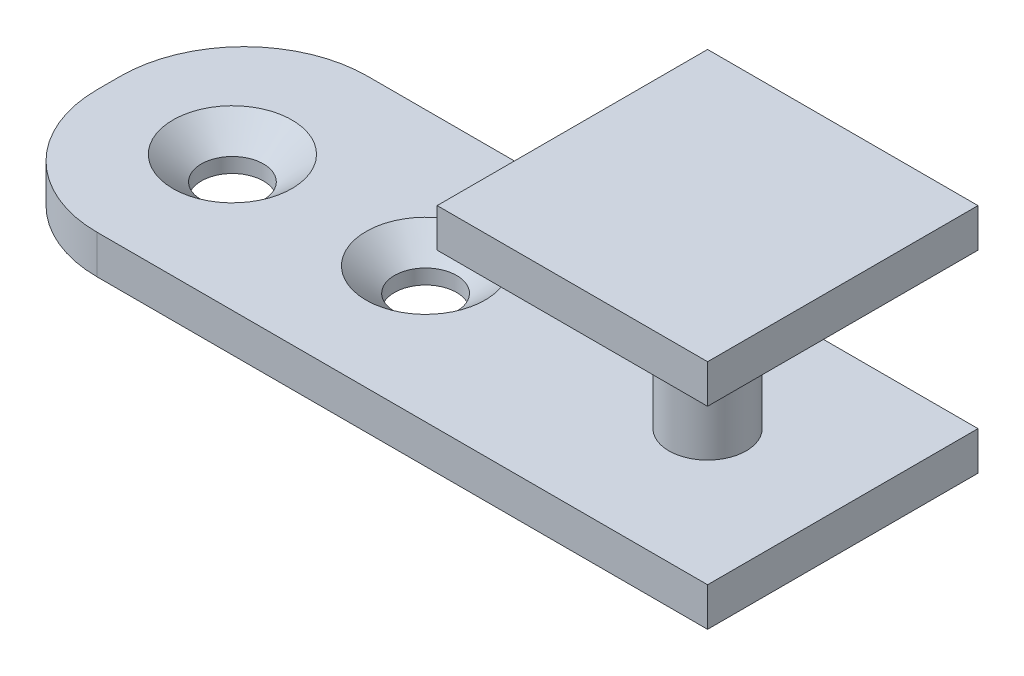
SolidWorks part; units mm, degrees
ref_plane "Front Plane" through (0, 0, 0) normal (0, 0, 1) x (1, 0, 0)
ref_plane "Top Plane" through (0, 0, 0) normal (0, 1, 0) x (1, 0, 0)
ref_plane "Right Plane" through (0, 0, 0) normal (1, 0, 0) x (0, 0, -1)
sketch "Sketch1" plane through (0, 0, 0) normal (0, 1, 0) x (1, 0, 0)
  circle A0 centre (0, 0) radius 3.175
  dimension "D1" = 6.35
extrude "Boss-Extrude1" add sketch "Sketch1" along normal blind 12.7
sketch "Sketch2" plane through (0, 12.7, 0) normal (0, 1, 0) x (1, 0, 0)
  line L1 (-11.1125, -11.1125) -> (11.1125, -11.1125)
  line L2 (-11.1125, -11.1125) -> (-11.1125, 11.1125)
  line L3 (-11.1125, 11.1125) -> (11.1125, 11.1125)
  line L4 (11.1125, -11.1125) -> (11.1125, 11.1125)
  line L5 (-11.1125, -11.1125) -> (11.1125, 11.1125) construction
  line L6 (-11.1125, 11.1125) -> (11.1125, -11.1125) construction
  point P0 (0, 0)
  dimension "D1" = 22.225
  dimension "D2" = 22.225
extrude "Boss-Extrude2" add sketch "Sketch2" along normal blind 3.175 contours L2 L3 L4 L1
ref_plane "Plane1" through (0, 6.35, 0) normal (0, -1, 0) x (-1, 0, 0)
mirror "Mirror1" about plane through (0, 6.35, 0) normal (0, -1, 0) of "Boss-Extrude2"
ref_axis "Axis1" through (0, 12.7, 0) along (0, -1, 0)
sketch "Sketch3" plane through (0, -3.175, 0) normal (0, -1, 0) x (1, 0, 0)
  line L0 (-11.1125, 11.1125) -> (11.1125, 11.1125) construction
  line L1 (-11.1125, -11.1125) -> (-39.0525, -11.1125)
  line L2 (-11.1125, -11.1125) -> (-11.1125, 11.1125)
  line L3 (-11.1125, 11.1125) -> (-39.0525, 11.1125)
  line L4 (-49.2125, -0.9525) -> (-49.2125, 0.9525)
  arc A0 (-49.2125, -0.9525) -> (-39.0525, -11.1125) centre (-39.0525, -0.9525) ccw
  arc A1 (-49.2125, 0.9525) -> (-39.0525, 11.1125) centre (-39.0525, 0.9525) cw
  point P11 (-49.2125, 11.1125)
  dimension "D2" = 10.16
  dimension "D1" = 38.1
extrude "Boss-Extrude3" add sketch "Sketch3" against normal up to surface (3.175 mm away) up to face at (0, 0, 3.175)
sketch "Sketch4" plane through (0, 0, 0) normal (0, 1, 0) x (1, 0, 0)
  point P0 (-39.0525, 0)
  point P1 (-23.1775, 0)
  point P2 (0, 0)
  point P4 (0, 0)
  dimension "D1" = 15.875
hole_wizard "CSK for #10 Flat Head Machine Screw (100)1" positions "Sketch5" profile "Sketch6" countersink size "#10" standard "ANSI Inch" end condition through all
sketch "Sketch5" plane through (0, 0, 0) normal (0, 1, 0) x (1, 0, 0)
  point P0 (-39.0525, 0)
  point P3 (-23.1775, 0)
sketch "Sketch6" plane through (-39.0525, 0, 0) normal (1, 0, 0) x (0, 0, 1)
  line L0 (0, 0) -> (0, 3.175)
  line L1 (0, 3.175) -> (2.5527, 3.175)
  line L2 (2.5527, 3.175) -> (2.5527, 1.9608)
  line L3 (2.5527, 1.9608) -> (4.8895, 0)
  line L5 (4.8895, 0) -> (0, 0)
  line L6 (-2.5527, 1.9608) -> (-4.8895, 0) construction
  line L11 (0, -6.35) -> (0, 107.95) construction
  dimension "Thru Hole Dia." = 5.1054
  dimension "Thru Hole Depth" = 3.175
  dimension "Near C'Sink Dia." = 9.779
  dimension "Near C'Sink Angle" = 100
